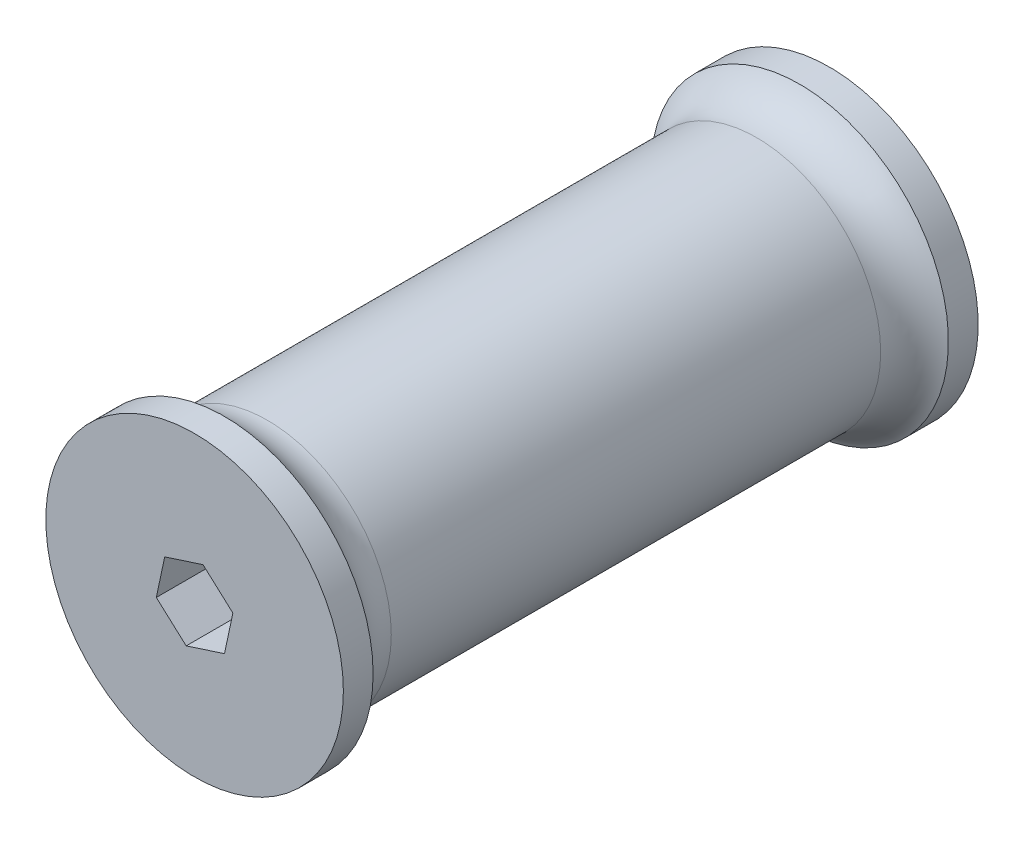
SolidWorks part; units mm, degrees
ref_plane "Alzado" through (0, 0, 0) normal (0, 0, 1) x (1, 0, 0)
ref_plane "Planta" through (0, 0, 0) normal (0, 1, 0) x (1, 0, 0)
ref_plane "Vista lateral" through (0, 0, 0) normal (1, 0, 0) x (0, 0, -1)
sketch "Croquis1" plane through (0, 0, 0) normal (0, 0, 1) x (1, 0, 0)
  circle A0 centre (0, 0) radius 15
  dimension "D1" = 30
extrude "Saliente-Extruir1" add sketch "Croquis1" along normal blind 3
sketch "Croquis2" plane through (0, 0, 3) normal (0, 0, 1) x (1, 0, 0)
  line L1 (3.014, -2.7184) -> (3.8612, 1.251)
  line L2 (3.8612, 1.251) -> (0.8472, 3.9694)
  line L3 (0.8472, 3.9694) -> (-3.014, 2.7184)
  line L4 (-3.014, 2.7184) -> (-3.8612, -1.251)
  line L5 (-3.8612, -1.251) -> (-0.8472, -3.9694)
  line L6 (-0.8472, -3.9694) -> (3.014, -2.7184)
  circle A1 centre (0, 0) radius 3.515 construction
  dimension "D1" = 7.03
sketch "Croquis3" plane through (0, 0, 0) normal (0, 0, -1) x (-1, 0, 0)
  circle A0 centre (0, 0) radius 9
  dimension "D1" = 18
extrude "Saliente-Extruir3" add sketch "Croquis3" along normal blind 58
sketch "Croquis4" plane through (0, 0, -58) normal (0, 0, -1) x (-1, 0, 0)
  circle A0 centre (0, 0) radius 15
  dimension "D1" = 30
extrude "Saliente-Extruir4" add sketch "Croquis4" along normal blind 3
sketch "Croquis5" plane through (0, 0, -61) normal (0, 0, -1) x (-1, 0, 0)
  line L1 (-0.107, 1.9971) -> (1.9918, 0.1805) construction
  line L2 (2.0456, 0.1339) -> (-0.1608, 2.0437)
  arc A0 (-0.1608, 2.0437) -> (2.0456, 0.1339) centre (0, 0) ccw
  circle A4 centre (0, 0) radius 15 construction
  point P3 (0, 0)
  point P5 (0, 0)
  point P7 (0.9424, 1.0888)
  point P10 (0.9424, 1.0888)
  dimension "D1" = 0.9424
  dimension "D4" = 4.1
  dimension "D2" = 2.0456
extrude "Cortar-Extruir1" cut sketch "Croquis5" against normal blind 8
sketch "Croquis8" plane through (0, 0, 0) normal (0, 0, -1) x (-1, 0, 0)
  circle A0 centre (0, 0) radius 12.5
  circle A1 centre (0, 0) radius 9 construction
  circle A2 centre (0, 0) radius 9
  dimension "D1" = 25
extrude "Saliente-Extruir7" add sketch "Croquis8" along normal up to surface (58 mm away) up to face at (-9, 0, -58)
fillet "Redondeo3" radius 5 2 edges at (-12.5, 0, -58) (12.5, 0, 0)
extrude "Cortar-Extruir2" cut sketch "Croquis2" against normal blind 40
